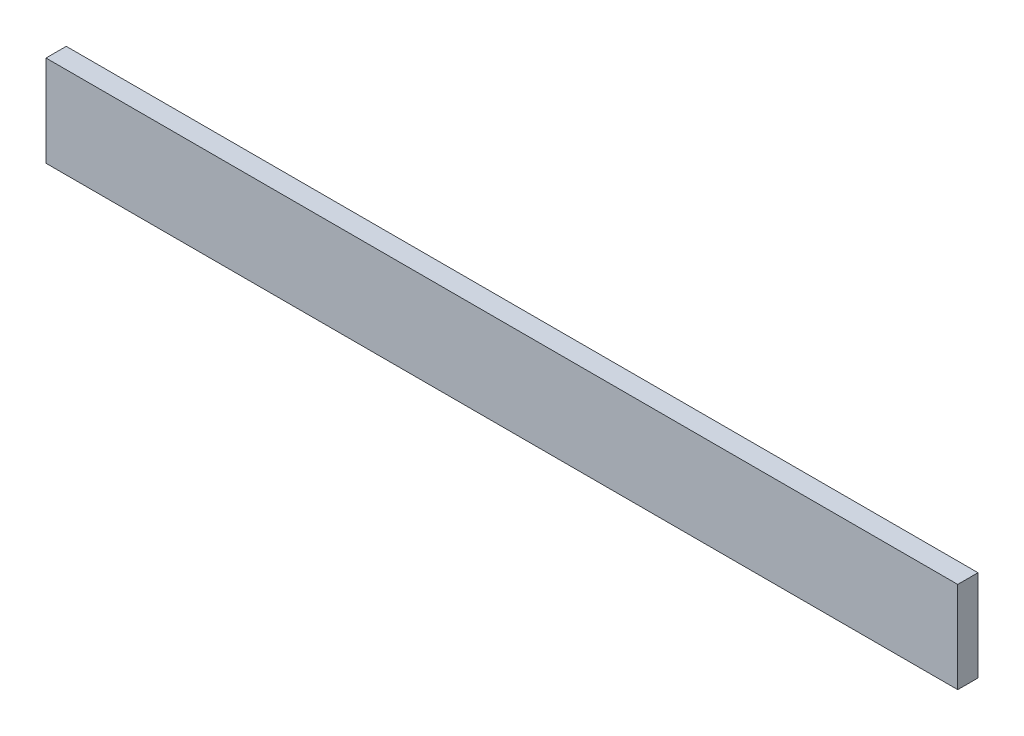
SolidWorks part; units mm, degrees
ref_plane "Front Plane" through (0, 0, 0) normal (0, 0, 1) x (1, 0, 0)
ref_plane "Top Plane" through (0, 0, 0) normal (0, 1, 0) x (1, 0, 0)
ref_plane "Right Plane" through (0, 0, 0) normal (1, 0, 0) x (0, 0, -1)
sketch "Sketch1" plane through (0, 0, 0) normal (0, 0, 1) x (1, 0, 0)
  line L1 (-745.3333, 45) -> (154.6667, 45)
  line L2 (-745.3333, 45) -> (-745.3333, -45)
  line L3 (-745.3333, -45) -> (154.6667, -45)
  line L4 (154.6667, 45) -> (154.6667, -45)
  point P0 (0, 0)
  dimension "D1" = 90
  dimension "D2" = 900
extrude "Boss-Extrude1" add sketch "Sketch1" along normal blind 10 and the other way blind 10
